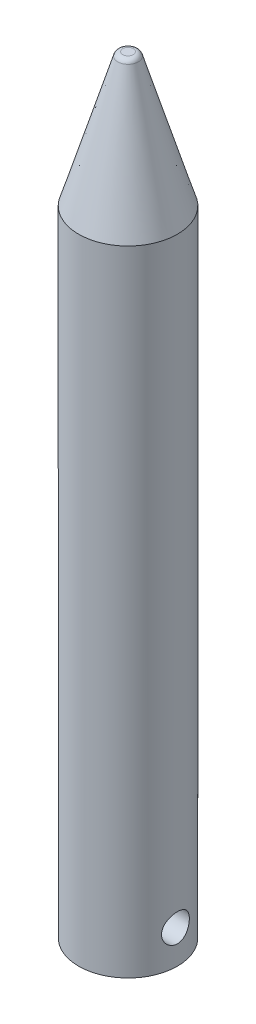
SolidWorks part; units mm, degrees
ref_plane "Front Plane" through (0, 0, 0) normal (0, 0, 1) x (1, 0, 0)
ref_plane "Top Plane" through (0, 0, 0) normal (0, 1, 0) x (1, 0, 0)
ref_plane "Right Plane" through (0, 0, 0) normal (1, 0, 0) x (0, 0, -1)
sketch "Sketch1" plane through (0, 0, 0) normal (0, 1, 0) x (1, 0, 0)
  circle A0 centre (0, 0) radius 9.398
  dimension "D1" = 18.796
extrude "Boss-Extrude1" add sketch "Sketch1" along normal blind 120.65
sketch "Sketch2" plane through (0, 0, 0) normal (0, 0, 1) x (1, 0, 0)
  line L8 (0, 120.65) -> (0, 146.05)
  line L9 (9.398, 120.65) -> (-9.398, 120.65) construction
  line L10 (1.9575, 145.3386) -> (9.398, 120.65)
  line L11 (9.398, 120.65) -> (0, 120.65)
  line L12 (1, 146.05) -> (0, 146.05)
  arc A3 (1, 146.05) -> (1.9575, 145.3386) centre (1, 145.05) cw
  dimension "D2" = 25.4
  dimension "D1" = 1
revolve "Revolve1" add sketch "Sketch2" angle 360 about L8
sketch "Sketch3" plane through (0, 0, 0) normal (1, 0, 0) x (0, 0, -1)
  line L1 (-9.398, 120.65) -> (-9.398, 0) construction
  circle A0 centre (0, 6.35) radius 2.65
  dimension "D1" = 5.3
  dimension "D3" = 9.398
  dimension "D2" = 6.35
extrude "Cut-Extrude1" cut sketch "Sketch3" against normal mid plane 60
